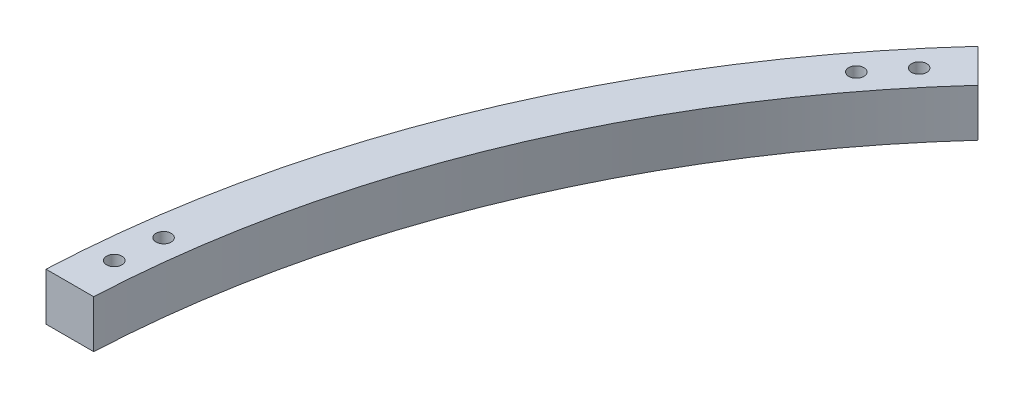
SolidWorks part; units mm, degrees
ref_plane "Front Plane" through (0, 0, 0) normal (0, 0, 1) x (1, 0, 0)
ref_plane "Top Plane" through (0, 0, 0) normal (0, 1, 0) x (1, 0, 0)
ref_plane "Right Plane" through (0, 0, 0) normal (1, 0, 0) x (0, 0, -1)
sketch "Sketch1" plane through (0, 0, 0) normal (0, 1, 0) x (1, 0, 0)
  line L1 (0, 220) -> (0, -220) construction
  line L6 (-220, 0) -> (220, 0) construction
  line L7 (-10, 219.7726) -> (-10, -219.7726) construction
  line L12 (-10, 219.7726) -> (-10, 209.7618)
  line L13 (-219.7726, 10) -> (219.7726, 10) construction
  line L14 (-219.7726, 10) -> (-209.7618, 10)
  line L15 (-155.5635, 155.5635) -> (155.5635, -155.5635) construction
  line L16 (-162.4738, 148.3316) -> (148.3316, -162.4738)
  arc A3 (-10, 219.7726) -> (-219.7726, 10) centre (0, 0) ccw
  arc A4 (-10, 209.7618) -> (-209.7618, 10) centre (0, 0) ccw
  arc A5 (-210, 0) -> (-209.7618, 10) centre (0, 0) ccw construction
  arc A6 (-220, 0) -> (-219.7726, 10) centre (0, 0) ccw construction
  circle A7 centre (0, 0) radius 215 construction
  dimension "D1" = 210
  dimension "D2" = 220
  dimension "D4" = 10
  dimension "D5" = 5
  dimension "D3" = 10
  dimension "D6" = 20
sketch "Sketch14" [suppressed] plane through (0, 0, 0) normal (0, 1, 0) x (1, 0, 0)
  line L0 (-200, 10) -> (200, 10) construction
  line L1 (-10, 200) -> (-10, -200) construction
  line L2 (-200, 10) -> (-189.7367, 10)
  line L3 (-10, 200) -> (-10, 189.7367)
  circle A0 centre (0, 0) radius 200 construction
  circle A1 centre (0, 0) radius 190 construction
  arc A2 (-10, 199.7498) -> (-199.7498, 10) centre (0, 0) ccw
  arc A3 (-10, 189.7367) -> (-189.7367, 10) centre (0, 0) ccw
sketch "roll" plane through (0, 0, 0) normal (0, 1, 0) x (1, 0, 0)
  line L0 (0, -195) -> (0, 195) construction
  dimension "D1" = 390
ref_axis "Axis1" through (0, -148.0362, 0) along (0, 1, 0)
extrude "base" add sketch "Sketch1" along normal mid plane 10 contours A4 L15 A3 L14 region at (-194.7302, 0, -80.6599)
sketch "Sketch25" plane through (0, 5, 0) normal (0, 1, 0) x (1, 0, 0)
  line L0 (-220, 0) -> (220, 0) construction
  line L1 (0, 220) -> (0, -220) construction
  line L2 (-220, 0) -> (220, 0)
  line L3 (0, 220) -> (0, -220)
  line L4 (0, 0) -> (-214.1819, 18.7385) construction
  line L5 (0, 0) -> (-170.571, 130.8837) construction
  line L6 (-155.5635, 155.5635) -> (155.5635, -155.5635) construction
  line L7 (-155.5635, 155.5635) -> (155.5635, -155.5635)
  line L8 (0, 0) -> (-164.6996, 138.1993) construction
  line L9 (0, 0) -> (-213.1606, 28.0631) construction
  circle A0 centre (0, 0) radius 215 construction
  circle A1 centre (0, 0) radius 215 construction
  dimension "D1" = 5
  dimension "D2" = 7.5
  dimension "D3" = 5
  dimension "D4" = 7.5
ref_plane "Plane1" through (0, 0, 0) normal (0.7071, 0, -0.7071) x (0.7071, 0, 0.7071)
hole_wizard "Ø3.1 (3.2) Diameter Hole1" positions "Sketch28" profile "Sketch29" hole size "Ø3.1" standard "ISO" end condition through all
sketch "Sketch28" plane through (0, 5, 0) normal (0, 1, 0) x (1, 0, 0)
  point P0 (-214.1819, 18.7385)
  point P3 (-164.6996, 138.1993)
  point P6 (-170.571, 130.8837)
  point P9 (-213.1606, 28.0631)
sketch "Sketch29" plane through (-214.1819, 5, -18.7385) normal (1, 0, 0) x (0, 0, 1)
  line L0 (0, 0) -> (0, 10)
  line L1 (0, 10) -> (1.6, 10)
  line L2 (1.6, 10) -> (1.6, 0)
  line L5 (1.6, 0) -> (0, 0)
  line L11 (0, -6.35) -> (0, 107.95) construction
  dimension "Thru Hole Dia." = 3.2
  dimension "Thru Hole Depth" = 10
